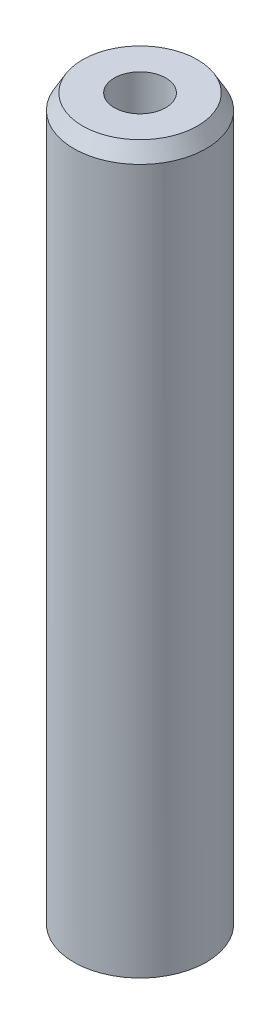
SolidWorks part; units mm, degrees
ref_plane "Front Plane" through (0, 0, 0) normal (0, 0, 1) x (1, 0, 0)
ref_plane "Top Plane" through (0, 0, 0) normal (0, 1, 0) x (1, 0, 0)
ref_plane "Right Plane" through (0, 0, 0) normal (1, 0, 0) x (0, 0, -1)
sketch "Sketch1" plane through (0, 0, 0) normal (0, 1, 0) x (1, 0, 0)
  circle A0 centre (0, 0) radius 10
  dimension "SHAFT_OD" = 20
extrude "Boss-Extrude1" add sketch "Sketch1" along normal blind 109.9978
sketch "Sketch2" plane through (0, 0, 0) normal (0, 1, 0) x (1, 0, 0)
  circle A0 centre (0, 0) radius 3.8888
  dimension "BORE_D" = 7.7776
extrude "Cut-Extrude1" cut sketch "Sketch2" along normal through all
chamfer "Chamfer1" distance 2.2975 angle 30 2 edges at (0, 109.9978, 10) (0, 0, 10) first distance on face at (0, 109.9978, 10) first distance on face at (0, 0, 3.8888)
